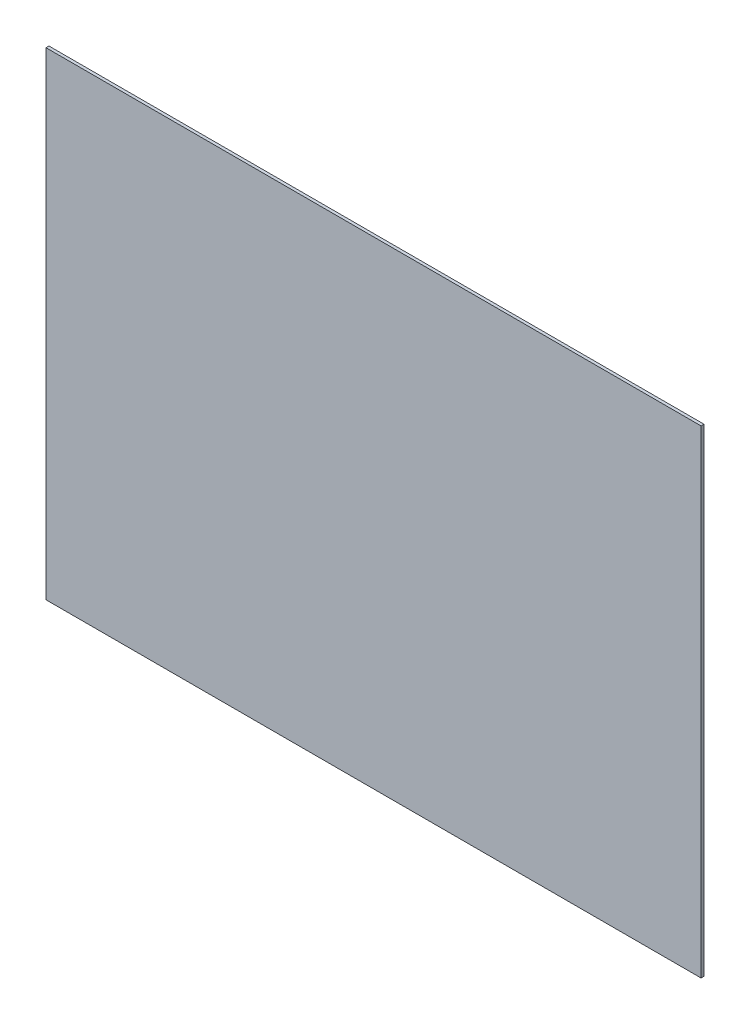
SolidWorks part; units mm, degrees
ref_plane "Front Plane" through (0, 0, 0) normal (0, 0, 1) x (1, 0, 0)
ref_plane "Top Plane" through (0, 0, 0) normal (0, 1, 0) x (1, 0, 0)
ref_plane "Right Plane" through (0, 0, 0) normal (1, 0, 0) x (0, 0, -1)
sketch "Sketch2" plane through (0, 0, 0) normal (0, 0, 1) x (1, 0, 0)
  line L1 (-225.24, 164.41) -> (225.24, 164.41)
  line L2 (-225.24, 164.41) -> (-225.24, -164.41)
  line L3 (-225.24, -164.41) -> (225.24, -164.41)
  line L4 (225.24, 164.41) -> (225.24, -164.41)
  line L5 (-225.24, 164.41) -> (225.24, -164.41) construction
  line L6 (-225.24, -164.41) -> (225.24, 164.41) construction
  point P0 (0, 0)
  dimension "Length 1" = 450.48
  dimension "Length 2" = 328.82
extrude "Boss-Extrude1" add sketch "Sketch2" along normal blind 2.032
